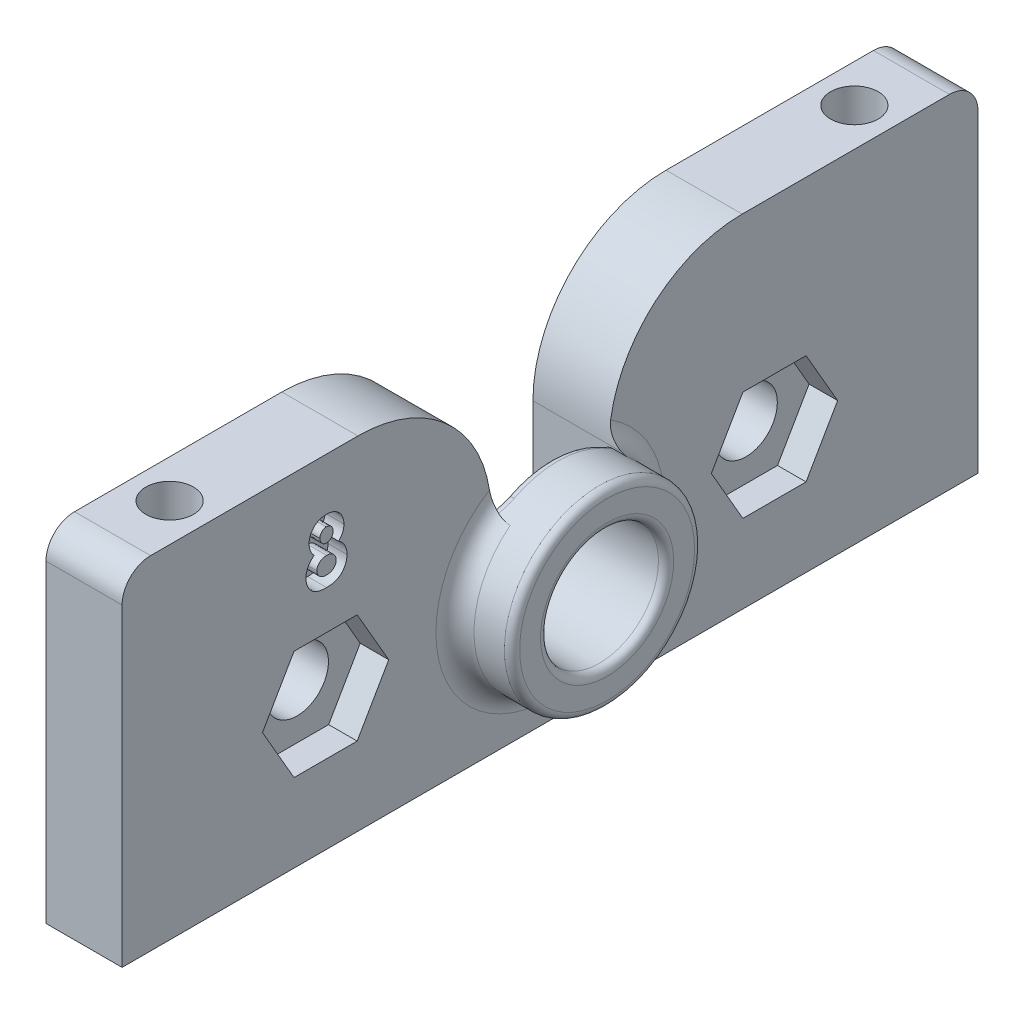
SolidWorks part; units mm, degrees
ref_plane "Front Plane" through (0, 0, 0) normal (0, 0, 1) x (1, 0, 0)
ref_plane "Top Plane" through (0, 0, 0) normal (0, 1, 0) x (1, 0, 0)
ref_plane "Right Plane" through (0, 0, 0) normal (1, 0, 0) x (0, 0, -1)
sketch "Sketch1" plane through (0, 0, 0) normal (1, 0, 0) x (0, 0, -1)
  line L1 (22.5, -9) -> (-22.5, -9)
  line L2 (22.5, -9) -> (22.5, 9)
  line L3 (22.5, 9) -> (-22.5, 9)
  line L4 (-22.5, -9) -> (-22.5, 9)
  line L5 (22.5, -9) -> (-22.5, 9) construction
  line L6 (22.5, 9) -> (-22.5, -9) construction
  point P0 (0, 0)
  dimension "D1" = 45
  dimension "D2" = 18
extrude "Boss-Extrude1" add sketch "Sketch1" along normal blind 4
sketch "Sketch2" plane through (4, 0, 0) normal (1, 0, 0) x (0, 0, -1)
  line L0 (-3.1, -2) -> (-3.1, 9)
  line L1 (22.5, 9) -> (-22.5, 9) construction
  line L2 (3.1, -2) -> (3.1, 9)
  line L3 (-22.5, -9) -> (22.5, -9) construction
  line L4 (3.1, 9) -> (-3.1, 9)
  line L6 (-9.7927, -9) -> (13.6616, -9) construction
  line L7 (-9.7927, -9) -> (-9.7927, -3.5) construction
  line L8 (-9.7927, -3.5) -> (13.6616, -3.5) construction
  line L9 (13.6616, -9) -> (13.6616, -3.5) construction
  circle A0 centre (-11.8, -2) radius 1.65
  arc A8 (-3.1, -2) -> (3.1, -2) centre (0, -2) ccw
  dimension "D3" = 3.3
  dimension "D4" = 6.2
  dimension "D5" = 11.8
  dimension "D2" = 7
  dimension "D1" = 7
  dimension "D6" = 5.5
extrude "Cut-Extrude1" cut sketch "Sketch2" against normal blind 5
mirror "Mirror1" about plane through (0, 0, 0) normal (0, 0, 1) of "Cut-Extrude1"
fillet "Fillet1" radius 1.5 2 edges at (2, 9, -22.5) (2, 9, 22.5)
sketch "Sketch6" plane through (4, 0, 0) normal (1, 0, 0) x (0, 0, -1)
  line L1 (-13.4599, -4.875) -> (-10.1401, -4.875)
  line L2 (-10.1401, -4.875) -> (-8.4802, -2)
  line L3 (-8.4802, -2) -> (-10.1401, 0.875)
  line L4 (-10.1401, 0.875) -> (-13.4599, 0.875)
  line L5 (-13.4599, 0.875) -> (-15.1198, -2)
  line L6 (-15.1198, -2) -> (-13.4599, -4.875)
  line L7 (13.4599, 0.875) -> (10.1401, 0.875)
  line L8 (10.1401, 0.875) -> (8.4802, -2)
  line L9 (8.4802, -2) -> (10.1401, -4.875)
  line L10 (10.1401, -4.875) -> (13.4599, -4.875)
  line L11 (13.4599, -4.875) -> (15.1198, -2)
  line L12 (15.1198, -2) -> (13.4599, 0.875)
  circle A1 centre (-11.8, -2) radius 2.875 construction
  circle A2 centre (11.8, -2) radius 2.875 construction
  dimension "D1" = 5.75
  dimension "D2" = 5.75
extrude "Cut-Extrude3" cut sketch "Sketch6" against normal blind 1.5
sketch "Sketch10" plane through (4, 0, 0) normal (1, 0, 0) x (0, 0, -1)
  line L0 (-3.1, 9) -> (-3.1, -2) construction
  line L1 (3.1, 9) -> (3.1, -2) construction
  arc A0 (-3.1, -2) -> (3.1, -2) centre (0, -2) ccw construction
sketch "Sketch3" plane through (4, 0, 0) normal (1, 0, 0) x (0, 0, -1)
  line L0 (-5, -2) -> (-8.4802, -2) construction
  line L3 (-3.1, -2) -> (-5, -2)
  line L4 (3.1, -2) -> (5, -2)
  line L5 (-10.1401, 0.875) -> (-8.4802, -2) construction
  line L6 (-9.9236, -4.5) -> (-4.3301, -4.5) construction
  line L7 (5, -2) -> (8.4802, -2) construction
  line L8 (-8.4802, -2) -> (-10.1401, 0.875) construction
  line L9 (9.9236, -4.5) -> (4.3301, -4.5) construction
  line L10 (8.4802, -2) -> (5, -2)
  line L11 (-22.5, 7.5) -> (-22.5, -9) construction
  line L12 (-22.5, -9) -> (22.5, -9) construction
  line L13 (-22.5, -9) -> (-22.5, -3.5) construction
  line L14 (-22.5, -3.5) -> (22.5, -3.5) construction
  line L15 (22.5, -9) -> (22.5, -3.5) construction
  line L16 (22.5, -9) -> (22.5, 7.5) construction
  line L17 (-22.5, -9) -> (22.5, -9) construction
  line L18 (-10.1401, -4.875) -> (-8.4802, -2) construction
  line L19 (10, -11.5) -> (-10, -11.5) construction
  line L20 (10, -11.5) -> (10, -3.5) construction
  line L21 (10, -3.5) -> (-10, -3.5) construction
  line L22 (-10, -11.5) -> (-10, -3.5) construction
  line L23 (10, -11.5) -> (-10, -3.5) construction
  line L24 (10, -3.5) -> (-10, -11.5) construction
  line L25 (10.1401, 0.875) -> (8.4802, -2) construction
  line L26 (10.1401, 0.875) -> (8.4802, -2) construction
  line L27 (-8.4802, -2) -> (-9.9236, -4.5) construction
  line L28 (8.4802, -2) -> (10.1401, -4.875) construction
  line L29 (8.4802, -2) -> (9.9236, -4.5) construction
  arc A1 (-5, -2) -> (5, -2) centre (0, -2) ccw
  arc A2 (-3.1, -2) -> (3.1, -2) centre (0, -2) ccw construction
  arc A3 (-3.1, -2) -> (3.1, -2) centre (0, -2) ccw
  arc A4 (-3.1, -2) -> (3.1, -2) centre (0, -2) ccw construction
  point P24 (0, -7.5)
  arc M6 (3.1, -2) -> (-3.1, -2) centre (0, -2) cw
  dimension "D1" = 5.5
  dimension "D2" = 8
  dimension "D3" = 5
  dimension "D4" = 2.5
  dimension "D8" = 20
extrude "Boss-Extrude4" [suppressed] add sketch "Sketch3" along normal blind 5 contours L3 A1 L4 M6
sketch "Sketch16" plane through (4, 0, 0) normal (1, 0, 0) x (0, 0, -1)
  circle A0 centre (0, -2) radius 3.1
  circle A1 centre (0, -2) radius 5
  arc A3 (-3.1, -2) -> (3.1, -2) centre (0, -2) ccw construction
  arc A4 (-5, -2) -> (5, -2) centre (0, -2) ccw construction
extrude "Boss-Extrude5" add sketch "Sketch16" along normal blind 3
sketch "Sketch11" [suppressed] plane through (0, 0, 0) normal (-1, 0, 0) x (0, 0, 1)
  line L0 (4, -2) -> (-4, -2) construction
  line L2 (-4, -2) -> (-4, 10.093)
  line L4 (-4, 10.093) -> (4, 10.093)
  line L5 (4, 10.093) -> (4, -2)
  circle A0 centre (0, -2) radius 4 construction
  arc A1 (4, -2) -> (-4, -2) centre (0, -2) cw
  dimension "D1" = 8
extrude "Cut-Extrude6" [suppressed] cut sketch "Sketch11" against normal up to surface (4 mm away)
sketch "Sketch4" plane through (0, -9, 0) normal (0, -1, 0) x (1, 0, 0)
  line L0 (2, 22.5) -> (2, -22.5) construction
  line L1 (4, 22.5) -> (0, 22.5) construction
  line L2 (4, -22.5) -> (0, -22.5) construction
  circle A0 centre (2, 18) radius 1.25
  circle A1 centre (2, -18) radius 1.25
  dimension "D1" = 2.5
  dimension "D2" = 2.5
  dimension "D3" = 18
  dimension "D4" = 18
extrude "Cut-Extrude2" cut sketch "Sketch4" against normal up to surface (18 mm away) up to face at (2, 9, 12.05)
fillet "Fillet9" radius 7 2 edges at (2, 9, 3.1) (2, 9, -3.1)
sketch "Sketch13" plane through (4, 0, 0) normal (1, 0, 0) x (0, 0, -1)
  text T0 "<b>8</b>"
extrude "Cut-Extrude7" cut sketch "Sketch13" against normal blind 1
fillet "Fillet18" radius 1 2 edges at (4, -0.0385, -3.1) (4, -0.0385, 3.1)
fillet "Fillet17" radius 1 1 edges at (4, -7, 0)
fillet "Fillet19" radius 0.4 5 edges at (7, -2, -5) (7, -2, -3.1) (3.5341, 2.0403, -2.9454) (3.734, 2.1565, 2.7792) (4, 3, 0)
